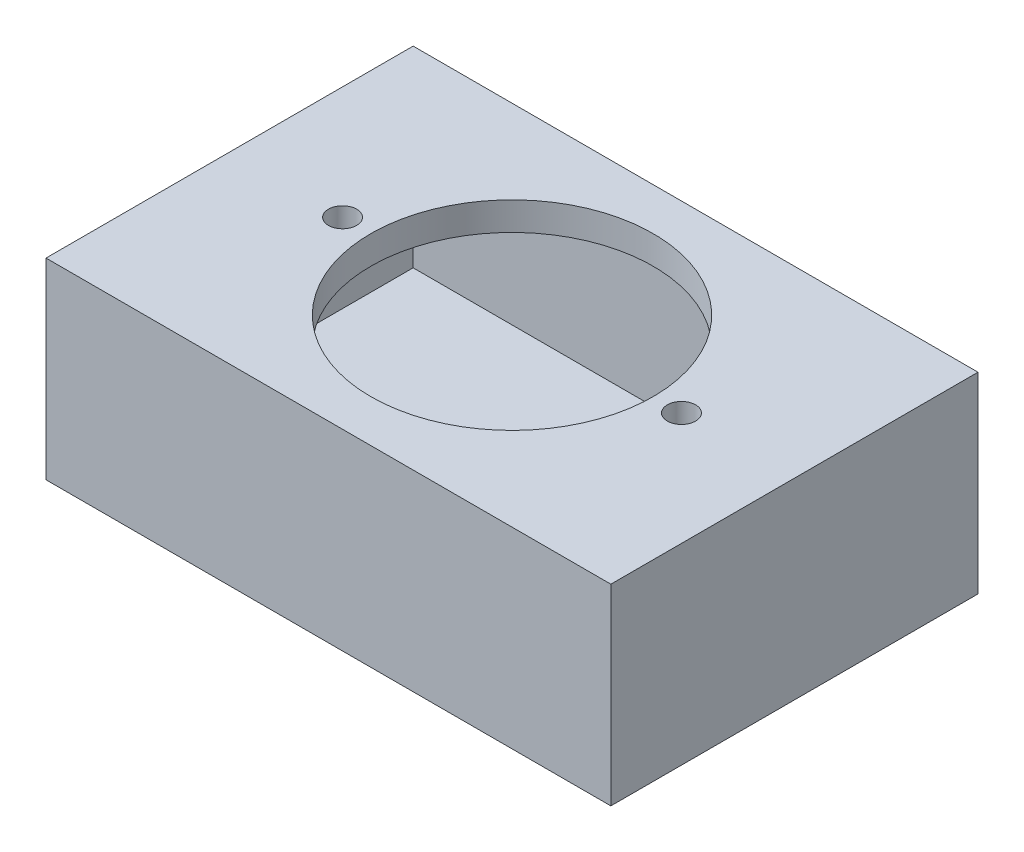
SolidWorks part; units mm, degrees
ref_plane "Front Plane" through (0, 0, 0) normal (0, 0, 1) x (1, 0, 0)
ref_plane "Top Plane" through (0, 0, 0) normal (0, 1, 0) x (1, 0, 0)
ref_plane "Right Plane" through (0, 0, 0) normal (1, 0, 0) x (0, 0, -1)
sketch "Sketch1" plane through (0, 0, 0) normal (0, 1, 0) x (1, 0, 0)
  line L1 (-100, 65) -> (100, 65)
  line L2 (-100, 65) -> (-100, -65)
  line L3 (-100, -65) -> (100, -65)
  line L4 (100, 65) -> (100, -65)
  line L5 (-100, 65) -> (100, -65) construction
  line L6 (-100, -65) -> (100, 65) construction
  point P0 (0, 0)
  dimension "D1" = 130
  dimension "D2" = 200
extrude "Boss-Extrude1" add sketch "Sketch1" along normal blind 58
shell "Shell1" thickness 10 removed face at (0, 58, 0)
sketch "Sketch2" plane through (0, 10, 0) normal (0, 1, 0) x (1, 0, 0)
  line L0 (0, -77.8873) -> (0, 72.769) construction
  line L1 (-134.4112, 0) -> (134.4112, 0) construction
  circle A0 centre (-15.5, 15.5) radius 1.5
  circle A1 centre (15.5, 15.5) radius 1.5
  circle A2 centre (-15.5, -15.5) radius 1.5
  circle A3 centre (15.5, -15.5) radius 1.5
  point P13 (0, 0)
  dimension "D1" = 3
  dimension "D2" = 28
  dimension "D3" = 28
extrude "Cut-Extrude1" cut sketch "Sketch2" against normal through all
sketch "Sketch3" plane through (0, 58, 0) normal (0, 1, 0) x (1, 0, 0)
  line L0 (100, -65) -> (100, 65) construction
  line L1 (100, -65) -> (100, 65)
  line L2 (-100, -65) -> (100, -65) construction
  line L3 (-100, 65) -> (-100, -65) construction
  line L4 (100, 65) -> (-100, 65) construction
  line L5 (-100, -65) -> (100, -65)
  line L6 (-100, 65) -> (-100, -65)
  line L7 (100, 65) -> (-100, 65)
extrude "Boss-Extrude2" add sketch "Sketch3" along normal blind 10
sketch "Sketch4" plane through (0, 68, 0) normal (0, 1, 0) x (1, 0, 0)
  line L0 (0, 0) -> (-60, 0)
  line L1 (-60, 0) -> (0, 0)
  line L2 (0, 0) -> (60, 0)
  circle A0 centre (0, 0) radius 50
  circle A1 centre (-60, 0) radius 5
  circle A2 centre (60, 0) radius 5
  dimension "D1" = 100
  dimension "D3" = 10
  dimension "D2" = 60
extrude "Cut-Extrude2" cut sketch "Sketch4" against normal up to next contours A1 | L0 A0 L2 | L2 A0 L0 | A2 region at (0, 68, 21.2207) region at (0, 68, -21.2207) region at (-64.8586, 68, 0)
